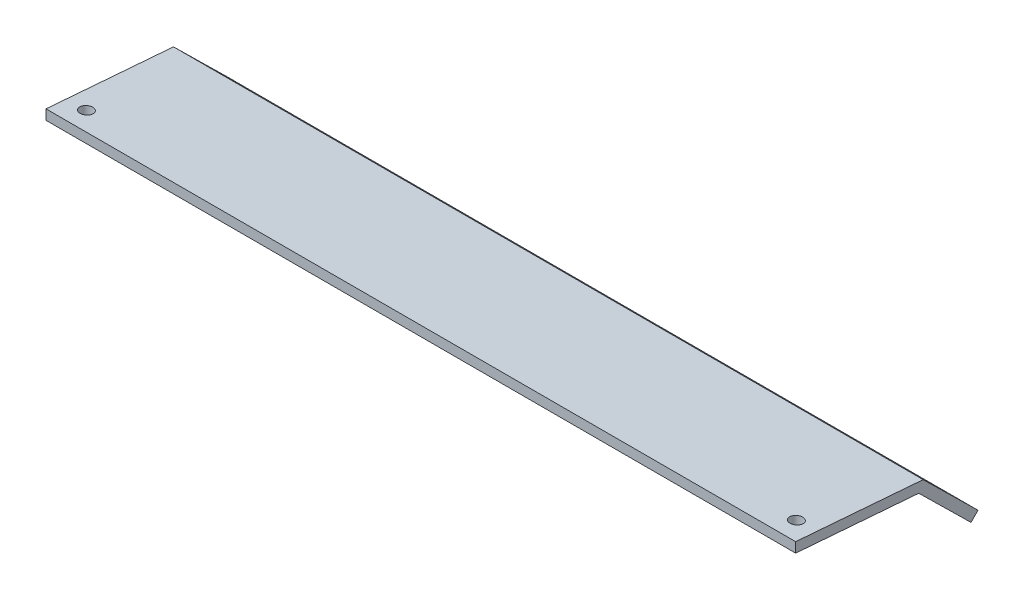
SolidWorks part; units mm, degrees
ref_plane "Front Plane" through (0, 0, 0) normal (0, 0, 1) x (1, 0, 0)
ref_plane "Top Plane" through (0, 0, 0) normal (0, 1, 0) x (1, 0, 0)
ref_plane "Right Plane" through (0, 0, 0) normal (1, 0, 0) x (0, 0, -1)
sketch "Sketch1" plane through (0, 0, 0) normal (1, 0, 0) x (0, 0, -1)
  line L8 (0, 0) -> (0, 3.1848)
  line L9 (0, 3.1848) -> (40.7629, -0.0223)
  line L10 (40.7629, -0.0223) -> (58.3049, -17.2609)
  line L11 (58.3049, -17.2609) -> (56.0795, -19.5255)
  line L12 (56.0795, -19.5255) -> (39.3618, -3.0969)
  line L13 (39.3618, -3.0969) -> (0, 0)
  point P2 (56.0795, -19.5255)
  dimension "D1" = 3.175
  dimension "D2" = 3.175
extrude "Boss-Extrude1" add sketch "Sketch1" along normal mid plane 239.7125
sketch "Sketch2" plane through (0, 3.1652, -0.249) normal (0, 0.9969, -0.0784) x (1, 0, 0)
  circle A0 centre (113.5062, 6.3549) radius 2.032
  circle A1 centre (-113.5063, 6.3549) radius 2.032
  dimension "D1" = 4.064
extrude "Cut-Extrude1" cut sketch "Sketch2" against normal through all
sketch "Sketch3" plane through (0, 20.367, -20.0148) normal (0, 0.7132, -0.7009) x (1, 0, 0)
  circle A0 centre (-113.5062, 48.6042) radius 2.032
  circle A1 centre (113.5063, 48.6042) radius 2.032
  dimension "D1" = 4.064
extrude "Cut-Extrude2" cut sketch "Sketch3" against normal blind 12.7
